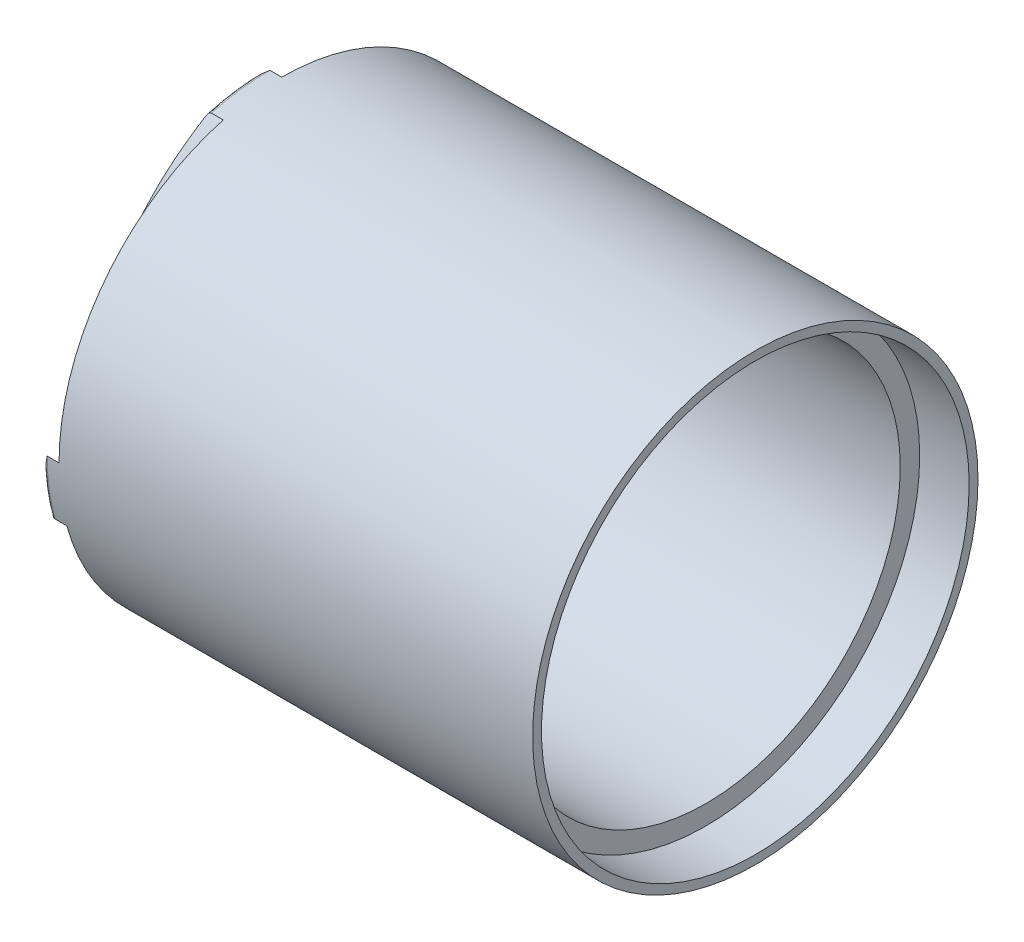
SolidWorks part; units mm, degrees
ref_plane "Front Plane" through (0, 0, 0) normal (0, 0, 1) x (1, 0, 0)
ref_plane "Top Plane" through (0, 0, 0) normal (0, 1, 0) x (1, 0, 0)
ref_plane "Right Plane" through (0, 0, 0) normal (1, 0, 0) x (0, 0, -1)
sketch "Sketch1" plane through (0, 0, 0) normal (1, 0, 0) x (0, 0, -1)
  circle A0 centre (0, 0) radius 31.5
  circle A1 centre (0, 0) radius 27.5
  dimension "D1" = 63
  dimension "D2" = 4
extrude "Extrude1" add sketch "Sketch1" along normal blind 67
sketch "Sketch2" plane through (0, 0, 0) normal (-1, 0, 0) x (0, 0, 1)
  circle A0 centre (0, 0) radius 31.5
  circle A1 centre (0, 0) radius 5
  circle A2 centre (0, 0) radius 16
  circle A3 centre (0, 23.75) radius 7.75
  arc A4 (0, 16) -> (-30.3957, 8.2676) centre (-5.716, -25.1391) ccw
  circle A5 centre (23.75, 0) radius 7.75
  arc A6 (16, 0) -> (8.2676, 30.3957) centre (-25.1391, 5.716) ccw
  circle A7 centre (0, -23.75) radius 7.75
  arc A8 (0, -16) -> (30.3957, -8.2676) centre (5.716, 25.1391) ccw
  circle A9 centre (-23.75, 0) radius 7.75
  arc A10 (-16, 0) -> (-8.2676, -30.3957) centre (25.1391, -5.716) ccw
  circle A11 centre (0, 12) radius 2
  circle A12 centre (12, 0) radius 2
  circle A13 centre (0, -12) radius 2
  circle A14 centre (-12, 0) radius 2
  circle M2 centre (0, 0) radius 27.5
  dimension "D1" = 10
  dimension "D2" = 63
  dimension "D3" = 32
  dimension "D5" = 4
  dimension "D4" = 12
extrude "Extrude2" add sketch "Sketch2" along normal blind 12 contours A9 A4 A0 M2 | A9 A2 A3 A4 M2 | A2 A1 | A5 A6 A3 A2 M2 | A6 A0 A3 M2 | A7 A8 A5 A2 M2 | A8 A0 A5 M2 | A9 A10 A7 A2 M2 | A10 A0 A7 M2
sketch "Sketch3" plane through (-12, 0, 0) normal (-1, 0, 0) x (0, 0, 1)
  circle A0 centre (0, 0) radius 14.5
  circle A1 centre (0, 0) radius 31.5
  dimension "D1" = 29
extrude "Extrude3" cut sketch "Sketch3" against normal blind 3
chamfer "Chamfer1" distance 7 angle 65.6 4 edges at (-9, 31.2227, 4.1705) (-9, -4.1705, 31.2227) (-9, -31.2227, -4.1705) (-9, 4.1705, -31.2227) first distance on face at (67, 0, -31.5)
fillet "Fillet1" radius 0.5 6 edges at (-2, 4.1705, -31.2227) (-2, 31.2227, 4.1705) (-2, -31.2227, -4.1705) (-2, -4.1705, 31.2227) (-12, 0, 5) (-12, 0, 14.5)
sketch "Sketch4" plane through (67, 0, 0) normal (1, 0, 0) x (0, 0, -1)
  circle A0 centre (0, 0) radius 30.25
  circle A1 centre (0, 0) radius 31.5
  circle M2 centre (0, 0) radius 27.5
  dimension "D1" = 63
  dimension "D2" = 60.5
extrude "Extrude4" cut sketch "Sketch4" against normal blind 7 contours A0 M2
sketch "Sketch5" plane through (0, 0, 0) normal (1, 0, 0) x (0, 0, -1)
  circle A0 centre (0, 0) radius 5
  circle A1 centre (0, 0) radius 8
  dimension "D1" = 10
  dimension "D2" = 3
extrude "Extrude5" add sketch "Sketch5" along normal blind 10.4
chamfer "Chamfer2" distance 2 angle 76.8 1 edges at (10.4, 0, -8) first distance on face at (10.4, 0, -8)
